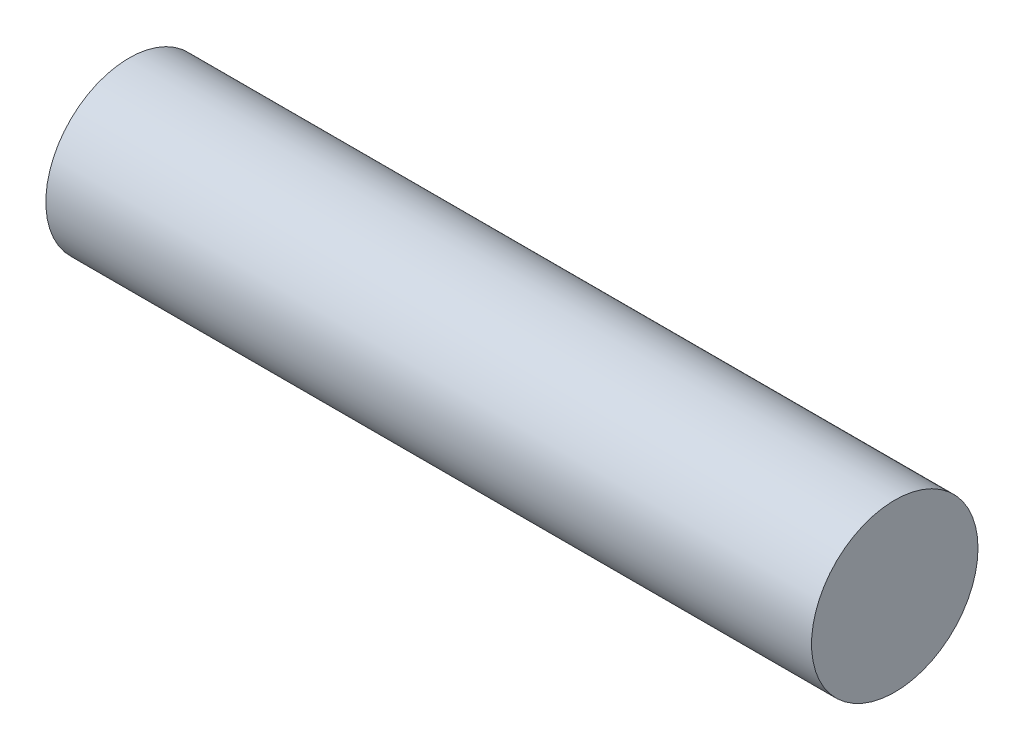
SolidWorks part; units mm, degrees
ref_plane "前视基准面" through (0, 0, 0) normal (0, 0, 1) x (1, 0, 0)
ref_plane "上视基准面" through (0, 0, 0) normal (0, 1, 0) x (1, 0, 0)
ref_plane "右视基准面" through (0, 0, 0) normal (1, 0, 0) x (0, 0, -1)
sketch "草图1" plane through (0, 0, 0) normal (1, 0, 0) x (0, 0, -1)
  circle A0 centre (0, 0) radius 2.5
  dimension "D1" = 5
extrude "凸台-拉伸1" add sketch "草图1" along normal blind 23
ref_axis "基准轴1" through (23, 0, 0) along (-1, 0, 0)
